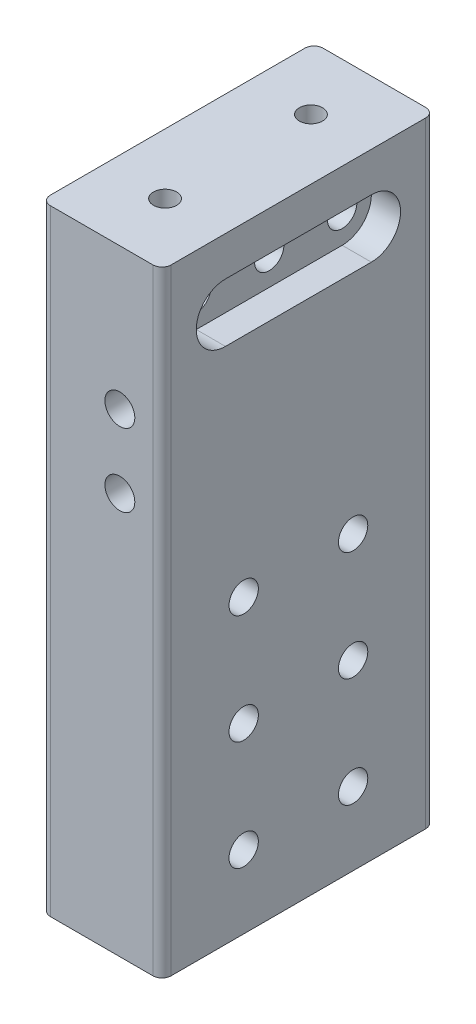
SolidWorks part; units mm, degrees
material "6061-T6 (SS)"
ref_plane "Front Plane" through (0, 0, 0) normal (0, 0, 1) x (1, 0, 0)
ref_plane "Top Plane" through (0, 0, 0) normal (0, 1, 0) x (1, 0, 0)
ref_plane "Right Plane" through (0, 0, 0) normal (1, 0, 0) x (0, 0, -1)
sketch "Sketch1" plane through (0, 0, 0) normal (0, 1, 0) x (1, 0, 0)
  line L1 (-10.5156, -23.7427) -> (10.5156, -23.7427)
  line L2 (-10.5156, -23.7427) -> (-10.5156, 23.7426)
  line L3 (-10.5156, 23.7426) -> (10.5156, 23.7426)
  line L4 (10.5156, -23.7427) -> (10.5156, 23.7426)
  line L5 (-10.5156, -23.7427) -> (10.5156, 23.7426) construction
  line L6 (-10.5156, 23.7426) -> (10.5156, -23.7427) construction
  point P0 (0, 0)
  dimension "D1" = 21.0312
  dimension "D2" = 47.4853
extrude "Boss-Extrude1" add sketch "Sketch1" along normal mid plane 101.6
sketch "Sketch2" plane through (0, 0, 23.7427) normal (0, 0, 1) x (1, 0, 0)
  line L5 (-10.5156, 50.8) -> (10.5156, 50.8) construction
  circle A1 centre (3.175, 19.05) radius 2.6035
  circle A2 centre (3.175, 31.75) radius 2.6035
  dimension "D3" = 19.05
  dimension "D1" = 7.3406
  dimension "D2" = 5.207
  dimension "D4" = 12.7
extrude "Cut-Extrude1" cut sketch "Sketch2" against normal through all
sketch "Sketch4" plane through (10.5156, 0, 0) normal (1, 0, 0) x (0, 0, -1)
  line L0 (-23.7427, 50.8) -> (23.7426, 50.8) construction
  circle A0 centre (-12.7, 44.45) radius 2.5527
  circle A1 centre (12.7, 44.45) radius 2.5527
  circle A2 centre (0, 44.45) radius 2.5527
  dimension "D5" = 5.1054
  dimension "D1" = 6.35
  dimension "D3" = 12.7
  dimension "D4" = 12.7
extrude "Cut-Extrude3" cut sketch "Sketch4" against normal through all
fillet "Fillet1" radius 1.5875 4 edges at (10.5156, 0, 23.7427) (-10.5156, 0, 23.7427) (-10.5156, 0, -23.7426) (10.5156, 0, -23.7426)
sketch "Sketch7" plane through (10.5156, 0, 0) normal (1, 0, 0) x (0, 0, -1)
  line L0 (-12.7, 44.45) -> (12.7, 44.45) construction
  line L1 (-12.7, 49.53) -> (12.7, 49.53)
  line L2 (-12.7, 39.37) -> (12.7, 39.37)
  arc A0 (-12.7, 49.53) -> (-12.7, 39.37) centre (-12.7, 44.45) ccw
  arc A1 (12.7, 39.37) -> (12.7, 49.53) centre (12.7, 44.45) ccw
  point P4 (0, 44.45)
  dimension "D1" = 5.08
extrude "Cut-Extrude5" cut sketch "Sketch7" against normal blind 5.08
sketch "Sketch8" plane through (0, 50.8, 0) normal (0, 1, 0) x (1, 0, 0)
  line L4 (-8.9281, -23.7427) -> (8.9281, -23.7427)
  line L5 (10.5156, -22.1552) -> (10.5156, 22.1551)
  line L6 (8.9281, 23.7426) -> (-8.9281, 23.7426)
  line L7 (-10.5156, 22.1551) -> (-10.5156, -22.1552)
  line L8 (-8.9281, -23.7427) -> (8.9281, -23.7427)
  line L9 (10.5156, -22.1552) -> (10.5156, 22.1551)
  line L10 (8.9281, 23.7426) -> (-8.9281, 23.7426)
  line L11 (-10.5156, 22.1551) -> (-10.5156, -22.1552)
  arc A4 (8.9281, -23.7427) -> (10.5156, -22.1552) centre (8.9281, -22.1552) ccw
  arc A5 (10.5156, 22.1551) -> (8.9281, 23.7426) centre (8.9281, 22.1551) ccw
  arc A6 (-8.9281, 23.7426) -> (-10.5156, 22.1551) centre (-8.9281, 22.1551) ccw
  arc A7 (-8.9281, 23.7426) -> (-10.5156, 22.1551) centre (-8.9281, 22.1551) ccw
  arc A8 (8.9281, -23.7427) -> (10.5156, -22.1552) centre (8.9281, -22.1552) ccw
  arc A9 (10.5156, 22.1551) -> (8.9281, 23.7426) centre (8.9281, 22.1551) ccw
  arc A10 (-10.5156, -22.1552) -> (-8.9281, -23.7427) centre (-8.9281, -22.1552) ccw
  arc A11 (-10.5156, -22.1552) -> (-8.9281, -23.7427) centre (-8.9281, -22.1552) ccw
  dimension "D1" = 0
extrude "Boss-Extrude2" add sketch "Sketch8" along normal blind 5.588
sketch "Sketch9" plane through (0, 56.388, 0) normal (0, 1, 0) x (1, 0, 0)
  line L0 (-10.5156, 0) -> (10.5156, 0) construction
  line L1 (-10.5156, 22.1551) -> (-10.5156, -22.1552) construction
  line L2 (10.5156, -22.1552) -> (10.5156, 22.1551) construction
  circle A0 centre (0, 12.7) radius 2.0193
  circle A2 centre (0, -12.7) radius 2.0193
  dimension "D2" = 4.0386
  dimension "D1" = 12.7
  dimension "D3" = 10.5156
extrude "Cut-Extrude6" cut sketch "Sketch9" against normal blind 5.08
sketch "Sketch10" plane through (10.5156, 0, 0) normal (1, 0, 0) x (0, 0, -1)
  line L0 (0, 0) -> (0, -50.8) construction
  line L1 (-22.1552, -50.8) -> (22.1551, -50.8) construction
  circle A0 centre (-9.525, -38.1) radius 2.5527
  circle A1 centre (-9.525, -19.05) radius 2.5527
  circle A2 centre (-9.525, 0) radius 2.5527
  circle A3 centre (9.525, 0) radius 2.5527
  circle A4 centre (9.525, -19.05) radius 2.5527
  circle A5 centre (9.525, -38.1) radius 2.5527
  point P12 (0, 0)
  point P13 (0, 0)
  dimension "D1" = 5.1054
  dimension "D6" = 12.7
  dimension "D2" = 19.05
  dimension "D3" = 19.05
  dimension "D4" = 9.525
  dimension "D5" = 9.525
extrude "Cut-Extrude7" cut sketch "Sketch10" against normal through all
